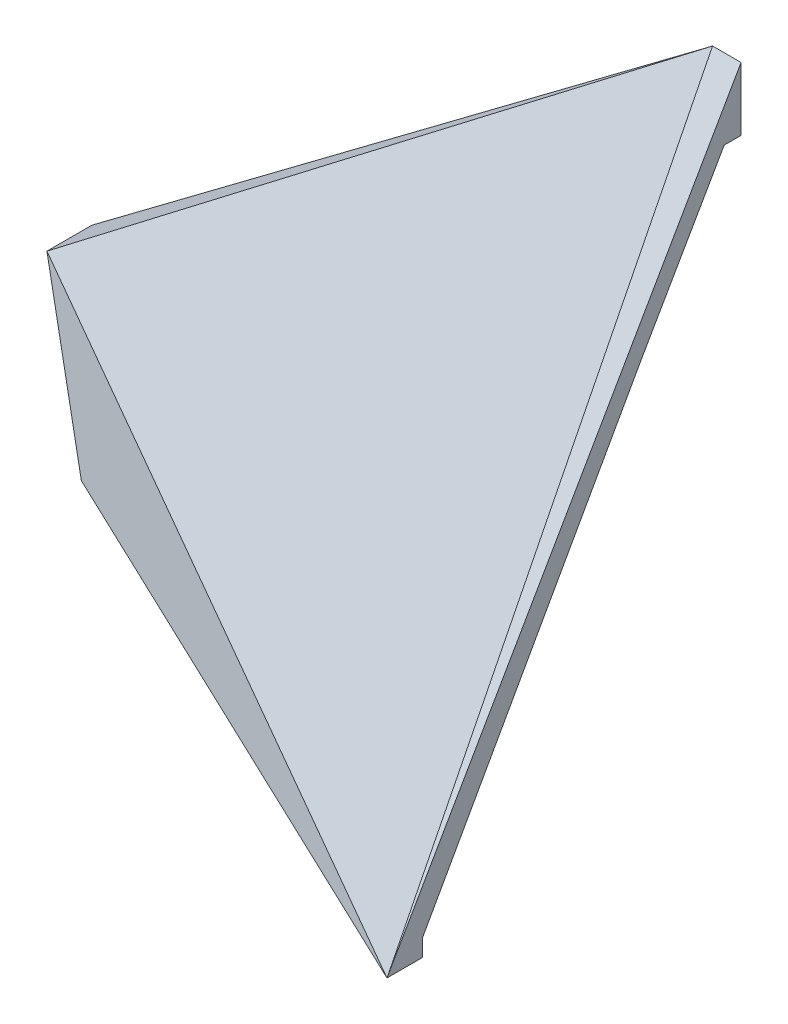
SolidWorks part; units mm, degrees
ref_plane "Plan de face" through (0, 0, 0) normal (0, 0, 1) x (1, 0, 0)
ref_plane "Plan de dessus" through (0, 0, 0) normal (0, 1, 0) x (1, 0, 0)
ref_plane "Plan de droite" through (0, 0, 0) normal (1, 0, 0) x (0, 0, -1)
sketch "Esquisse1" plane through (0, 0, 0) normal (0, 0, 1) x (1, 0, 0)
  line L0 (0, 0) -> (0, 300)
  line L1 (0, 300) -> (-400, 0) construction
  line L2 (-400, 0) -> (0, 0)
  line L3 (0, 300) -> (0, 377.9)
  line L4 (0, 377.9) -> (-400, 77.9)
  line L5 (-400, 77.9) -> (-400, 0)
  dimension "D1" = 300
  dimension "D2" = 400
  dimension "D3" = 77.9
extrude "Boss.-Extru.1" add sketch "Esquisse1" along normal blind 220
sketch "Esquisse2" plane through (0, 0, 0) normal (1, 0, 0) x (0, 0, -1)
  line L0 (-240, 400) -> (-10, 0)
  line L1 (-220, 0) -> (0, 0) construction
  line L2 (-10, 0) -> (0, 0)
  line L3 (0, 0) -> (0, 377.9)
  line L4 (0, 377.9) -> (0, 400)
  line L5 (0, 400) -> (-240, 400)
  line L6 (-10, 0) -> (-10, 400) construction
  dimension "D1" = 400
  dimension "D2" = 230
  dimension "D3" = 10
extrude "Enlèv. mat.-Extru.1" cut sketch "Esquisse2" against normal through all
sketch "Esquisse9" plane through (0, 0, 0) normal (0, -1, 0) x (-1, 0, 0)
  line L0 (0, -10) -> (546, -270)
  line L1 (546, -270) -> (546, -10)
  line L2 (546, -10) -> (0, -10)
  dimension "D1" = 546
  dimension "D2" = 260
extrude "Enlèv. mat.-Extru.7" cut sketch "Esquisse9" against normal through all
sketch "Esquisse10" plane through (0, 0, 220) normal (0, 0, 1) x (1, 0, 0)
  line L0 (-400, 77.9) -> (-385, 89.15)
  line L1 (-16.9101, 365.2174) -> (-400, 77.9) construction
  line L2 (-385, 89.15) -> (15, -825.85)
  line L3 (15, -825.85) -> (-400, -825.85)
  line L4 (-400, -825.85) -> (-400, 77.9)
  line L5 (-385, 89.15) -> (-385, -825.85) construction
  dimension "D1" = 915
  dimension "D2" = 400
  dimension "D3" = 15
extrude "Enlèv. mat.-Extru.8" cut sketch "Esquisse10" against normal through all
ref_plane "Plan1" through (2.4204, -3.9014, 6.98) normal (-0.2897, 0.467, -0.8355) x (-0.9571, -0.1413, 0.2529)
sketch "Esquisse11" plane through (2.4204, -3.9014, 6.98) normal (-0.2897, 0.467, -0.8355) x (-0.9571, -0.1413, 0.2529)
  line L0 (411.5229, 185.1573) -> (386.8228, 107.3384)
  line L1 (386.8228, 107.3384) -> (375.386, 85.273)
  line L2 (375.386, 85.273) -> (2.5289, 4.879)
  line L3 (2.5289, 4.879) -> (4.0117, 426.1361)
  line L4 (4.0117, 426.1361) -> (20.1967, 426.1361)
  line L5 (20.1967, 426.1361) -> (411.5229, 185.1573)
extrude "Enlèv. mat.-Extru.9" cut sketch "Esquisse11" along normal through all
shell "Coque2" thickness 10
sketch "Esquisse12" plane through (0, 0, 0) normal (1, 0, 0) x (0, 0, -1)
  line L0 (-220, 0) -> (-31.0265, 0)
  line L1 (-220, 0) -> (-10, 0) construction
  line L2 (-31.0265, 0) -> (-31.0265, 10)
  line L3 (-31.0265, 10) -> (-161.2681, 243.0136)
  line L4 (-161.2681, 243.0136) -> (-210, 327.7647)
  line L5 (-220, 0) -> (-220, 365.2174) construction
  line L6 (-220, 327.7647) -> (-220, 0)
  line L7 (-210, 327.7647) -> (-220, 327.7647)
extrude "Enlèv. mat.-Extru.10" cut sketch "Esquisse12" against normal blind 10
sketch "Esquisse13" plane through (0, 0, 220) normal (0, 0, 1) x (1, 0, 0)
  line L0 (-10, 327.7647) -> (-13.9241, 327.7647)
  line L1 (-13.9241, 327.7647) -> (-223.7203, 197.6098)
  line L2 (-223.7203, 197.6098) -> (-372.6657, 85.9007)
  line L3 (-372.6657, 85.9007) -> (-339.4851, 10)
  line L4 (-339.4851, 10) -> (-339.4851, 0)
  line L5 (-346.0273, 0) -> (-10, 0) construction
  line L6 (-339.4851, 0) -> (0, 0)
  line L7 (0, 0) -> (0, 327.7647)
  line L9 (0, 327.7647) -> (-10, 327.7647)
  line L10 (0, 243.0136) -> (0, 327.7647) construction
extrude "Enlèv. mat.-Extru.11" cut sketch "Esquisse13" against normal blind 10
sketch "Esquisse14" plane through (0, 10, 0) normal (0, 1, 0) x (1, 0, 0)
  line L0 (-10, -31.0265) -> (-50.0889, -44.9278)
  line L1 (-339.4851, -182.7355) -> (-339.4851, -210)
  line L2 (-339.4851, -210) -> (-10, -210)
  line L3 (-10, -210) -> (-10, -31.0265)
  line L4 (-50.0889, -44.9278) -> (-339.4851, -182.7355)
extrude "Enlèv. mat.-Extru.12" cut sketch "Esquisse14" against normal blind 10
sketch "Esquisse15" plane through (5.3175, -8.5712, 15.3347) normal (0.2897, -0.467, 0.8355) x (0.9571, 0.1413, -0.2529)
  line L7 (-47.2662, 320.279) -> (-65.8608, 331.058)
  line L8 (-64.4708, 65.8766) -> (-46.0038, 78.1975)
  line L9 (-324.2649, 182.8874) -> (-323.3758, 173.5369)
  line L14 (-46.0038, 290.1804) -> (-48.1042, 340.2615)
  line L15 (-48.1042, 340.2615) -> (-224.0889, 249.0465)
  line L16 (-224.0889, 249.0465) -> (-332.6093, 177.3765)
  line L17 (-332.6093, 177.3765) -> (-49.6197, 59.7011)
  line L18 (-49.6197, 59.7011) -> (-46.0038, 59.1155)
  line L19 (-46.0038, 59.1155) -> (-46.0038, 290.1804)
  line L20 (-46.0038, 290.1804) -> (-47.2662, 320.279)
  line L21 (-65.8608, 331.058) -> (-224.0889, 249.0465)
  line L22 (-224.0889, 249.0465) -> (-324.2649, 182.8874)
  line L23 (-323.3758, 173.5369) -> (-64.4708, 65.8766)
  line L25 (-46.0038, 78.1975) -> (-46.0038, 290.1804)
  point P5 (-46.0038, 58.1975)
  dimension "D1" = 30
extrude "Enlèv. mat.-Extru.13" cut sketch "Esquisse15" against normal blind 5
sketch "Esquisse16" plane through (8.181, 0, 17.1802) normal (0.4299, 0, 0.9029) x (0.9029, 0, -0.4299)
  line L5 (-191.7545, 15) -> (-191.1197, 21.1392)
  line L6 (-384.5862, 61.5863) -> (-390.0166, 54.6322)
  line L7 (-375.1849, 24.0005) -> (-360.827, 15)
  line L10 (-394.3746, 63.6327) -> (-370.827, 15)
  line L11 (-370.827, 15) -> (-161.7545, 15)
  line L12 (-161.7545, 15) -> (-394.3746, 63.6327)
  line L13 (-390.0166, 54.6322) -> (-375.1849, 24.0005)
  line L14 (-360.827, 15) -> (-191.7545, 15)
  line L15 (-191.1197, 21.1392) -> (-384.5862, 61.5863)
  dimension "D1" = 15
extrude "Enlèv. mat.-Extru.14" cut sketch "Esquisse16" against normal blind 5
chamfer "Chanfrein1" distance 5 angle 45 13 edges at (-40.162, 148.0393, 112.6571) (-48.9995, 48.837, 60.273) (-181.738, 70.8447, 118.6028) (-306.0644, 103.5532, 179.9967) (-258.5499, 143.5264, 185.8633) (-134.8887, 226.4579, 189.3363) (-50.2688, 270.0441, 184.3556) (-40.7661, 253.6065, 171.8727) (-326.2267, 19.5002, 170.884) (-339.4038, 39.3164, 177.1588) (-343.6478, 58.1093, 179.1798) (-253.8597, 41.3628, 136.4235) (-166.8096, 18.0696, 94.9711)
mirror "Symétrie1" about plane through (0, 0, 220) normal (0, 0, 1) of bodies 115
sketch "Esquisse17" plane through (0, 0, 0) normal (0, 1, 0) x (1, 0, 0)
  line L1 (0, -220) -> (-468.9682, -220)
  line L2 (0, -220) -> (0, 63.4854)
  line L3 (0, 63.4854) -> (-468.9682, 63.4854)
  line L4 (-468.9682, -220) -> (-468.9682, 63.4854)
extrude "Enlèv. mat.-Extru.15" cut sketch "Esquisse17" along normal through all
